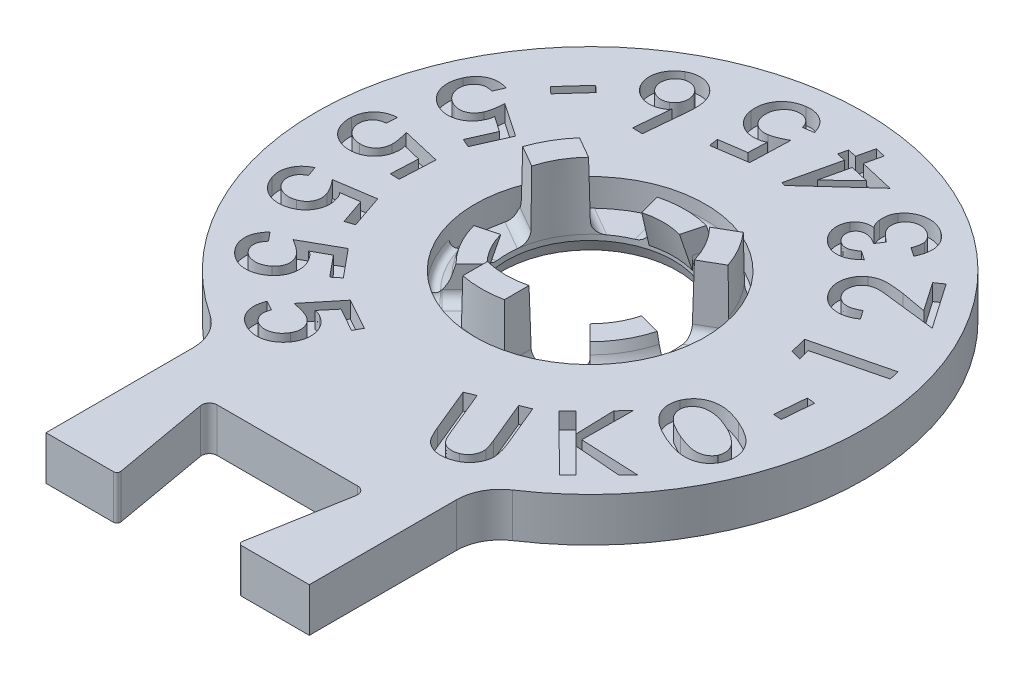
SolidWorks part; units mm, degrees
ref_plane "Front Plane" through (0, 0, 0) normal (0, 0, 1) x (1, 0, 0)
ref_plane "Top Plane" through (0, 0, 0) normal (0, 1, 0) x (1, 0, 0)
ref_plane "Right Plane" through (0, 0, 0) normal (1, 0, 0) x (0, 0, -1)
sketch "Sketch1" plane through (0, 0, 0) normal (0, 1, 0) x (1, 0, 0)
  line L0 (-6, 6) -> (-6, -13.2915)
  line L1 (-6, -19) -> (-2.7023, -19)
  line L2 (6, -19) -> (6, -13.2915)
  line L3 (6, 6) -> (-6, 6)
  line L4 (-6, -13.2915) -> (-6, -19)
  line L5 (6, -13.2915) -> (6, 6)
  line L6 (0, -19) -> (0, 0) construction
  line L7 (-2.6007, -19) -> (-3.5, -13.9) construction
  line L8 (-3.5, -13.9) -> (0, -13.9) construction
  line L9 (-2.7023, -19) -> (-3.6192, -13.8)
  line L10 (-3.6192, -13.8) -> (0, -13.8)
  line L11 (-2.6992, -19.0174) -> (-3.6192, -13.8) construction
  line L12 (2.7023, -19) -> (6, -19)
  line L13 (3.6192, -13.8) -> (0, -13.8)
  line L14 (2.7023, -19) -> (3.6192, -13.8)
  circle A0 centre (0, 0) radius 4
  dimension "D1" = 8
  dimension "D5" = 6
  dimension "D7" = 80
  dimension "D2" = 25
  dimension "D3" = 6
  dimension "D4" = 12
  dimension "D8" = 3.5
  dimension "D9" = 5.1
  dimension "D10" = 0.1
extrude "Boss-Extrude1" add sketch "Sketch1" along normal blind 2
sketch "Sketch2" plane through (0, 0, 0) normal (0, 1, 0) x (1, 0, 0)
  circle A0 centre (0, 0) radius 12.5
  circle A1 centre (0, 0) radius 3.8
  dimension "D1" = 25
  dimension "D2" = 7.6
extrude "Boss-Extrude2" add sketch "Sketch2" along normal blind 2
sketch "Sketch3" plane through (0, 0, 0) normal (0, -1, 0) x (1, 0, 0)
  line L0 (-3, 0) -> (-3, 4)
  line L1 (3, 0) -> (3, 4)
  arc A0 (-3, 0) -> (3, 0) centre (0, 0) ccw
  arc A1 (-3, 4) -> (3, 4) centre (0, 0) ccw
extrude "Boss-Extrude3" [suppressed] add sketch "Sketch3" along normal blind 4
fillet "Fillet1" [suppressed] radius 0.5
fillet "Fillet2" [suppressed] radius 1
sketch "Sketch4" plane through (0, 2, 0) normal (0, 1, 0) x (1, 0, 0)
  line L0 (-6, -10.9659) -> (-6, -19) construction
  line L1 (-6, -18.8) -> (6, -18.8)
  line L2 (-6, -18.8) -> (-6, -19)
  line L3 (-6, -19) -> (6, -19)
  line L4 (6, -18.8) -> (6, -19)
  dimension "D1" = 0.2
extrude "Cut-Extrude1" cut sketch "Sketch4" against normal blind 4
fillet "Fillet3" radius 0.35 2 edges at (3.6192, 1, 13.8) (-3.6192, 1, 13.8)
fillet "Fillet4" radius 0.15 2 edges at (2.7375, 1, 18.8) (-2.7375, 1, 18.8)
sketch "Sketch5" plane through (0, 0, 0) normal (0, 1, 0) x (1, 0, 0)
  circle A1 centre (0, 0) radius 3
  circle A2 centre (0, 0) radius 2.1
  dimension "D1" = 4.2
  dimension "D2" = 6
extrude "Boss-Extrude4" [suppressed] add sketch "Sketch5" along normal blind 13
fillet "Fillet5" [suppressed] radius 2
fillet "Fillet6" radius 2 2 edges at (-6, 1, 10.9659) (6, 1, 10.9659)
sketch "Sketch6" plane through (0, 2, 0) normal (0, 1, 0) x (1, 0, 0)
  circle A0 centre (0, 0) radius 3.5
  dimension "D1" = 7
extrude "Boss-Extrude5" [suppressed] add sketch "Sketch6" along normal blind 2 contours A0
sketch "Sketch7" [suppressed] plane through (0, 4, 0) normal (0, 1, 0) x (1, 0, 0)
  circle A0 centre (0, 0) radius 3.15
extrude "Cut-Extrude3" [suppressed] cut sketch "Sketch7" against normal blind 3.2
fillet "Fillet7" [suppressed] radius 2
fillet "Fillet8" [suppressed] radius 1
fillet "Fillet9" [suppressed] radius 0.1
sketch "Sketch8" plane through (0, 2, 0) normal (0, 1, 0) x (1, 0, 0)
  line L0 (0, 0) -> (0, 3.9) construction
  line L1 (-0.5, 3.65) -> (0, 2.65)
  line L2 (-0.5, 4.15) -> (0.5, 4.15)
  line L3 (-0.5, 4.15) -> (-0.5, 3.65)
  line L4 (-0.5, 3.65) -> (0.5, 3.65) construction
  line L5 (0.5, 4.15) -> (0.5, 3.65)
  line L6 (-0.5, 4.15) -> (0.5, 3.65) construction
  line L7 (-0.5, 3.65) -> (0.5, 4.15) construction
  line L8 (0, 2.65) -> (0.5, 3.65)
  dimension "D1" = 3.9
  dimension "D2" = 0.5
  dimension "D3" = 1
  dimension "D4" = 1
extrude "Boss-Extrude6" [suppressed] add sketch "Sketch8" against normal blind 2
pattern_circular "CirPattern1" [suppressed] count 5 over 360 of bodies 109
sketch "Sketch11" plane through (0, 2, 0) normal (0, 1, 0) x (1, 0, 0)
  circle A0 centre (0, 0) radius 4
  circle A1 centre (0, 0) radius 5
  dimension "D1" = 8
  dimension "D2" = 10
extrude "Boss-Extrude7" [suppressed] add sketch "Sketch11" along normal blind 2 draft 3
sketch "Sketch13" plane through (0, 2, 0) normal (0, 1, 0) x (1, 0, 0)
  circle A0 centre (0, 0) radius 5 construction
  circle A1 centre (0, 0) radius 5.25
  dimension "D1" = 10
  dimension "D2" = 10.5
extrude "Cut-Extrude5" cut sketch "Sketch13" against normal blind 1.25
fillet "Fillet10" [suppressed] radius 0.2
sketch "Sketch12" plane through (0, 0, 0) normal (1, 0, 0) x (0, 0, -1)
  line L0 (0, 0) -> (-4, 0) construction
  line L1 (-10.4253, 0) -> (12.5, 0) construction
  line L2 (-3.8, 0) -> (3.8, 0) construction
  line L3 (0, 0) -> (0, 2) construction
  line L4 (3.8, 2) -> (-3.8, 2) construction
  line L5 (-4, 0) -> (-3.4, 2) construction
  line L6 (-3.4, 2) -> (-4.4, 2) construction
  line L7 (-4.4, 2) -> (-5, 0) construction
  line L8 (-5, 0) -> (-4, 0) construction
  line L9 (-4, 0) -> (-4.0344, -0.0135)
  line L10 (5, 0) -> (4, 0)
  line L11 (4, 0) -> (3.4, 2)
  line L12 (4.4, 2) -> (5, 0)
  line L13 (3.4, 2) -> (4.4, 2) construction
  line L14 (3.4, 2) -> (3.325, 2.25)
  line L15 (3.325, 2.25) -> (4.325, 2.25)
  line L16 (4.325, 2.25) -> (4.4, 2)
  dimension "D1" = 0
  dimension "D2" = 3.4
  dimension "D3" = 1
  dimension "D4" = 4
  dimension "D5" = 0.25
revolve "Revolve2" add sketch "Sketch12" angle 30 mid plane about L3
pattern_circular "CirPattern2" count 3 over 360 about axis through (0, 2, 0) along (0, -1, 0) of "Revolve2"
chamfer "Chamfer1" distance 0.5 angle 20 1 edges at (0, 0, 3.8) first distance on face at (0, 0.7083, 0)
fillet "Fillet13" [suppressed] radius 0.25
sketch "Sketch15" plane through (0, 0, 0) normal (0, -1, 0) x (1, 0, 0)
  line L0 (0, 0) -> (2.186, 0) construction
  line L1 (-1, 4.899) -> (-1, 3.6661)
  line L2 (1, -4.899) -> (1, -3.6661) construction
  line L3 (1, 4.899) -> (1, 3.6661)
  line L4 (-1, -4.899) -> (-1, -3.6661) construction
  arc A0 (-1, -3.6661) -> (1, -3.6661) centre (0, 0) ccw construction
  arc A1 (-1, -4.899) -> (1, -4.899) centre (0, 0) ccw construction
  arc A2 (-1, 4.899) -> (1, 4.899) centre (0, 0) cw
  arc A3 (-1, 3.6661) -> (1, 3.6661) centre (0, 0) cw
  point P4 (0, -5)
  point P12 (0, 5)
  dimension "D1" = 7.6
  dimension "D2" = 10
  dimension "D3" = 1
  dimension "D4" = 1
extrude "Boss-Extrude8" add sketch "Sketch15" against normal blind 3 draft 1 from offset 0.75 offset against normal yes
pattern_circular "CirPattern3" count 3 over 360 about axis through (0, 0.75, 0) along (0, 1, 0) of "Boss-Extrude8"
sketch "Sketch16" plane through (0, 2, 0) normal (0, 1, 0) x (1, 0, 0)
  line L0 (-3.4702, -13.925) -> (0.4048, 0) construction
  line L1 (0.4048, 0) -> (3.4702, -13.925) construction
  arc A0 (2.857, -11.1395) -> (-2.7055, -11.1772) centre (0, 0) ccw construction
  arc A1 (-3.2021, -13.8) -> (-3.5467, -14.2108) centre (-3.2021, -14.15) ccw construction
  arc A2 (3.5467, -14.2108) -> (3.2021, -13.8) centre (3.2021, -14.15) ccw construction
  text T0 "<b>UK0-123456-55555</b>" font "Century Gothic" height 3.5
  dimension "D1" = 23
extrude "Cut-Extrude6" cut sketch "Sketch16" against normal blind 0.75
fillet "Fillet14" radius 1.5 3 edges at (0, 0.75, -4.775) (-4.1353, 0.75, 2.3875) (4.1353, 0.75, 2.3875)
fillet "Fillet15" radius 0.25 3 edges at (0, 0.8939, -5.25) (-4.5466, 0.8939, 2.625) (4.5466, 0.8939, 2.625)
fillet "Fillet16" radius 0.5 6 edges at (-3.1997, 0.75, 3.1997) (-4.3708, 0.75, 1.1712) (4.3708, 0.75, 1.1712) (3.1997, 0.75, 3.1997) (1.1712, 0.75, -4.3708) (-1.1712, 0.75, -4.3708)
fillet "Fillet17" radius 1 3 edges at (4.3301, 0.75, -2.5) (-4.3301, 0.75, -2.5) (0, 0.75, 5)
fillet "Fillet18" radius 0.5 6 edges at (3.3191, 0.75, -3.071) (4.3191, 0.75, -1.339) (1, 0.75, 4.41) (-1, 0.75, 4.41) (-4.3191, 0.75, -1.339) (-3.3191, 0.75, -3.071)
pattern_linear "LPattern1" [suppressed] count 3 spacing 35 count 4 spacing 27.5 of bodies 135 120
